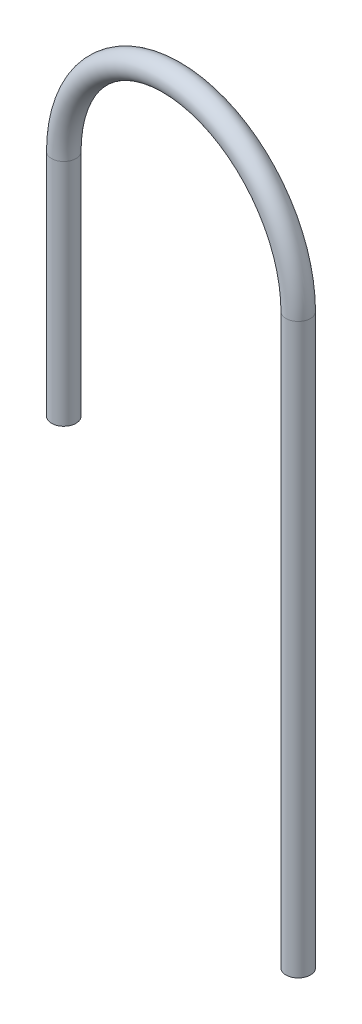
SolidWorks part; units mm, degrees
material "PE faible/moyenne densité"
ref_plane "Front" through (0, 0, 0) normal (0, 0, 1) x (1, 0, 0)
ref_plane "Top" through (0, 0, 0) normal (0, 1, 0) x (1, 0, 0)
ref_plane "Right" through (0, 0, 0) normal (1, 0, 0) x (0, 0, -1)
sketch3d "Esquisse3D1"
  line L0 (14, 165, -59.25) -> (14, 221.325, -59.25)
  line L1 (76.8149, 221.325, -54.0281) -> (76.8149, 81.65, -54.0281)
  arc A0 (14, 221.325, -59.25) -> (76.8149, 221.325, -54.0281) centre (45.4075, 221.325, -56.6391) ccw
  circle A1 centre (76.8149, 89.65, -54.0281) radius 1.1 construction
  point P3 (48.0184, 221.325, -88.0465)
  point P9 (76.8149, 88.55, -54.0281)
  dimension "D4" = 139.675
  dimension "D1" = 165
  dimension "D2" = 14
  dimension "D3" = 59.25
  dimension "D5" = 81.65
sweep "Balayage-Mince1" add path "Esquisse3D1" circular profile diameter 6 parameters "D1"=1, "D3"=6
equation "\"D4@Esquisse3D1\"=140-((\"D5@Esquisse3D1\"-81)/2)"
